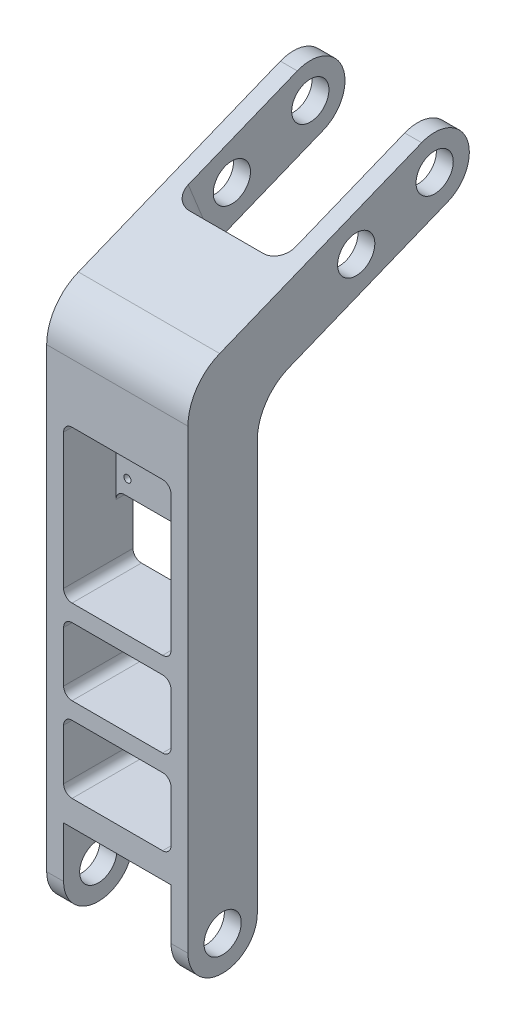
SolidWorks part; units mm, degrees
ref_plane "前视基准面" through (0, 0, 0) normal (0, 0, 1) x (1, 0, 0)
ref_plane "上视基准面" through (0, 0, 0) normal (0, 1, 0) x (1, 0, 0)
ref_plane "右视基准面" through (0, 0, 0) normal (1, 0, 0) x (0, 0, -1)
sketch "草图1" plane through (0, 0, 0) normal (0, 0, 1) x (1, 0, 0)
  line L0 (0, 0) -> (0, 40)
  line L1 (0, 40) -> (83.5, 40)
  line L2 (83.5, 40) -> (83.5, 0)
  line L3 (83.5, 0) -> (73.5, 0)
  line L4 (73.5, 0) -> (73.5, 30)
  line L5 (73.5, 30) -> (10, 30)
  line L6 (10, 30) -> (10, 0)
  line L7 (10, 0) -> (0, 0)
  dimension "D1" = 63.5
  dimension "D2" = 10
  dimension "D3" = 30
  dimension "D4" = 10
extrude "凸台-拉伸1" add sketch "草图1" along normal blind 41
sketch "草图2" plane through (83.5, 0, 0) normal (1, 0, 0) x (0, 0, -1)
  line L0 (-41, 0) -> (0, 0)
  arc A0 (-41, 0) -> (0, 0) centre (-20.5, 0) ccw
extrude "凸台-拉伸2" add sketch "草图2" against normal blind 10
sketch "草图3" plane through (83.5, 0, 0) normal (1, 0, 0) x (0, 0, -1)
  circle A0 centre (-20.5, 0) radius 11
  dimension "D1" = 22
extrude "切除-拉伸1" cut sketch "草图3" against normal blind 10
ref_plane "基准面4" through (41.75, 0, 0) normal (1, 0, 0) x (0, 0, -1)
mirror "镜向1" about plane through (41.75, 0, 0) normal (1, 0, 0) of "凸台-拉伸2", "切除-拉伸1"
sketch "草图4" plane through (0, 40, 0) normal (0, 1, 0) x (1, 0, 0)
  line L0 (83.5, 0) -> (0, 0) construction
  line L1 (0, 0) -> (83.5, 0)
  line L2 (0, 0) -> (0, -41)
  line L3 (0, -41) -> (83.5, -41)
  line L4 (83.5, 0) -> (83.5, -41)
  line L5 (83.5, -41) -> (0, -41) construction
  line L6 (41.75, -41) -> (41.75, 5.4834) construction
extrude "凸台-拉伸3" add sketch "草图4" along normal blind 250
sketch "草图5" plane through (0, 0, 41) normal (0, 0, 1) x (1, 0, 0)
  line L0 (83.5, 0) -> (83.5, 290) construction
  line L1 (15, 45) -> (68.5, 45)
  line L2 (10, 50) -> (10, 80)
  line L3 (15, 85) -> (68.5, 85)
  line L4 (73.5, 50) -> (73.5, 80)
  line L5 (0, 290) -> (0, 0) construction
  line L6 (10, 30) -> (73.5, 30) construction
  line L23 (10, 100) -> (10, 130)
  line L24 (15, 95) -> (68.5, 95)
  line L25 (73.5, 100) -> (73.5, 130)
  line L26 (15, 135) -> (68.5, 135)
  line L27 (10, 150) -> (10, 180)
  line L28 (15, 145) -> (68.5, 145)
  line L29 (73.5, 150) -> (73.5, 180)
  line L30 (15, 185) -> (68.5, 185)
  arc A0 (68.5, 45) -> (73.5, 50) centre (68.5, 50) ccw
  arc A1 (68.5, 85) -> (73.5, 80) centre (68.5, 80) cw
  arc A2 (15, 45) -> (10, 50) centre (15, 50) cw
  arc A3 (10, 80) -> (15, 85) centre (15, 80) cw
  arc A20 (10, 130) -> (15, 135) centre (15, 130) cw
  arc A21 (15, 95) -> (10, 100) centre (15, 100) cw
  arc A22 (68.5, 95) -> (73.5, 100) centre (68.5, 100) ccw
  arc A23 (68.5, 135) -> (73.5, 130) centre (68.5, 130) cw
  arc A24 (10, 180) -> (15, 185) centre (15, 180) cw
  arc A25 (15, 145) -> (10, 150) centre (15, 150) cw
  arc A26 (68.5, 145) -> (73.5, 150) centre (68.5, 150) ccw
  arc A27 (68.5, 185) -> (73.5, 180) centre (68.5, 180) cw
  point P10 (73.5, 45)
  point P13 (73.5, 85)
  dimension "D4" = 5
  dimension "D1" = 10
  dimension "D2" = 10
  dimension "D3" = 40
  dimension "D5" = 15
  dimension "D6" = 3
extrude "切除-拉伸2" cut sketch "草图5" against normal blind 309
sketch "草图7" plane through (83.5, 0, 0) normal (1, 0, 0) x (0, 0, -1)
  line L0 (0, 262.3452) -> (112.4864, 307.7926)
  line L1 (112.4864, 307.7926) -> (97.1275, 345.8071)
  line L2 (97.1275, 345.8071) -> (-41, 290)
  line L3 (-41, 290) -> (0, 262.3452)
  line L4 (0, 0) -> (0, 290) construction
  circle A1 centre (-20.5, 0) radius 11 construction
  point P3 (104.807, 326.7999)
  dimension "D1" = 350
  dimension "D2" = 112
  dimension "D3" = 41
extrude "凸台-拉伸5" add sketch "草图7" against normal up to surface (83.5 mm away) up to face at (0, 11, 20.5)
sketch "草图8" plane through (41.75, 0, 0) normal (1, 0, 0) x (0, 0, -1)
  line L0 (0, 232.3452) -> (0, 192.3452)
  line L1 (55, 192.3452) -> (55, 210.3452)
  line L2 (0, 192.3452) -> (55, 192.3452)
  line L5 (55, 210.3452) -> (0, 232.3452)
  line L7 (0, 0) -> (0, 262.3452) construction
  dimension "D1" = 70
  dimension "D2" = 55
  dimension "D3" = 40
  dimension "D4" = 18
extrude "凸台-拉伸6" add sketch "草图8" along normal mid plane 83.5
fillet "圆角1" radius 8 1 edges at (41.75, 192.3452, -55)
sketch "草图10" plane through (83.5, 0, 0) normal (1, 0, 0) x (0, 0, -1)
  circle A0 centre (47, 200.3452) radius 5.5
  dimension "D1" = 11
extrude "切除-拉伸3" cut sketch "草图10" against normal blind 92
sketch "草图11" [suppressed] plane through (52.25, 0, 0) normal (1, 0, 0) x (0, 0, -1)
  line L0 (55, 283.0172) -> (15, 241.915)
  line L1 (55, 242.0172) -> (55, 298.0172) construction
  line L2 (15, 241.915) -> (15, 227.0172)
  line L3 (0, 227.0172) -> (40, 227.0172) construction
  line L4 (15, 227.0172) -> (64.4389, 227.0172)
  line L5 (64.4389, 227.0172) -> (55, 283.0172)
  line L6 (0, 0) -> (0, 243.0172) construction
  dimension "D1" = 15
  dimension "D2" = 15
fillet "圆角2" [suppressed] radius 5
sketch "草图13" plane through (41.75, 0, 0) normal (1, 0, 0) x (0, 0, -1)
  circle A0 centre (47, 200.3452) radius 6
  circle A1 centre (47, 200.3452) radius 5
  dimension "D1" = 10
extrude "凸台-拉伸8" [suppressed] add sketch "草图13" along normal mid plane 1
sketch "草图14" plane through (41.75, 0, 0) normal (1, 0, 0) x (0, 0, -1)
  line L0 (97.1275, 345.8071) -> (112.4864, 307.7926)
  arc A0 (97.1275, 345.8071) -> (112.4864, 307.7926) centre (104.807, 326.7999) cw
extrude "凸台-拉伸9" add sketch "草图14" against normal mid plane 83.5
sketch "草图15" plane through (83.5, 0, 0) normal (1, 0, 0) x (0, 0, -1)
  line L0 (0, 262.3452) -> (112.4864, 307.7926) construction
  circle A0 centre (104.807, 326.7999) radius 11
  circle A1 centre (58.4478, 308.0696) radius 11
  dimension "D1" = 22
  dimension "D2" = 22
  dimension "D3" = 50
  dimension "D4" = 20.5
extrude "切除-拉伸5" cut sketch "草图15" against normal mid plane 185
sketch "草图16" plane through (0, 263.5448, 106.479) normal (0, 0.9272, 0.3746) x (1, 0, 0)
  line L0 (83.5, 240.0967) -> (0, 240.0967) construction
  line L1 (10, 240.0967) -> (73.5, 240.0967)
  line L2 (10, 240.0967) -> (10, 140.0967)
  line L3 (10, 140.0967) -> (73.5, 140.0967)
  line L4 (73.5, 240.0967) -> (73.5, 140.0967)
  line L5 (83.5, 219.5967) -> (83.5, 70.6214) construction
  line L6 (0, 70.6214) -> (0, 219.5967) construction
  dimension "D1" = 10
  dimension "D2" = 10
  dimension "D3" = 100
extrude "切除-拉伸6" cut sketch "草图16" against normal blind 65
sketch "草图17" plane through (10, 0, 0) normal (1, 0, 0) x (0, 0, -1)
  circle A0 centre (58.4478, 308.0696) radius 9.5
  circle A1 centre (58.4478, 308.0696) radius 7.5
  dimension "D1" = 15
extrude "凸台-拉伸10" [suppressed] add sketch "草图17" against normal blind 4
sketch "草图18" [suppressed] plane through (73.5, 0, 0) normal (-1, 0, 0) x (0, 0, 1)
  circle A0 centre (-35.6394, 310.5764) radius 7.5
  circle A1 centre (-35.6394, 310.5764) radius 9.5
extrude "凸台-拉伸11" [suppressed] add sketch "草图18" against normal blind 4
fillet "圆角3" radius 30 2 edges at (41.75, 290, 41) (41.75, 262.3452, 0)
extrude "切除-拉伸7" cut sketch "草图8<2>" against normal mid plane 75.5
sketch "草图8<2>" plane through (41.75, 0, 0) normal (1, 0, 0) x (0, 0, -1) same geometry as "草图8"
fillet "圆角4" [suppressed] radius 8
sketch "草图19" plane through (83.5, 0, 0) normal (1, 0, 0) x (0, 0, -1)
  line L1 (0, 232.3452) -> (70.1752, 232.3452)
  line L2 (0, 232.3452) -> (0, 190.676)
  line L3 (0, 190.676) -> (70.1752, 190.676)
  line L4 (70.1752, 232.3452) -> (70.1752, 190.676)
extrude "切除-拉伸8" cut sketch "草图19" against normal blind 90.5
sketch "草图20" plane through (0, 0, 0) normal (0, 0, -1) x (-1, 0, 0)
  line L1 (-66.75, 214) -> (-16.75, 214) construction
  line L2 (-66.75, 214) -> (-66.75, 194) construction
  line L3 (-66.75, 194) -> (-16.75, 194) construction
  line L4 (-16.75, 214) -> (-16.75, 194) construction
  line L5 (-66.75, 214) -> (-16.75, 194) construction
  line L6 (-66.75, 194) -> (-16.75, 214) construction
  point P0 (-41.75, 204)
  dimension "D1" = 41.75
  dimension "D2" = 204
  dimension "D3" = 20
  dimension "D4" = 50
hole_wizard "M5 螺纹孔的螺纹孔钻头1" positions "3D草图1" profile "草图21" hole size "M5" standard "GB"
sketch3d "3D草图1"
  point P0 (66.75, 214, 0)
  point P3 (16.75, 214, 0)
  point P6 (16.75, 194, 0)
  point P9 (66.75, 194, 0)
sketch "草图21" plane through (66.75, 214, 0) normal (1, 0, 0) x (0, 1, 0)
  line L0 (0, 0) -> (0, 11.2618)
  line L1 (0, 11.2618) -> (2.1, 10)
  line L2 (2.1, 10) -> (2.1, 0)
  line L5 (2.1, 0) -> (0, 0)
  line L10 (0, 11.2618) -> (-2.1, 10) construction
  line L11 (0, -6.35) -> (0, 107.95) construction
  dimension "孔直径" = 4.2
  dimension "孔深度" = 10
  dimension "导头角度" = 118
fillet "圆角5" radius 10 2 edges at (10, 297.0187, -31.0959) (73.5, 297.0187, -31.0959)
sketch "草图22" plane through (0, 0, 41) normal (0, 0, 1) x (1, 0, 0)
  line L2 (10, 190) -> (10, 230)
  line L3 (15, 235) -> (68.5, 235)
  line L4 (73.5, 190) -> (73.5, 230)
  line L5 (10, 190) -> (10, 177.9025)
  line L6 (10, 180) -> (10, 150) construction
  line L7 (73.5, 150) -> (73.5, 180) construction
  line L8 (10, 177.9025) -> (73.5, 177.9025)
  line L9 (73.5, 177.9025) -> (73.5, 190)
  arc A0 (10, 230) -> (15, 235) centre (15, 230) cw
  arc A1 (68.5, 235) -> (73.5, 230) centre (68.5, 230) cw
  point P10 (73.5, 235)
  point P13 (73.5, 185)
  dimension "D3" = 5
  dimension "D2" = 50
extrude "切除-拉伸9" cut sketch "草图22" against normal blind 31
sketch "草图23" plane through (83.5, 0, 0) normal (1, 0, 0) x (0, 0, -1)
  line L0 (-20.5, 0) -> (104.807, 326.7999) construction
  line L1 (104.807, 326.7999) -> (-20.5, 276.1726) construction
  line L2 (-20.5, 276.1726) -> (-20.5, 0) construction
  line L3 (97.1275, 345.8071) -> (-22.2382, 297.5803) construction
  dimension "D1" = 112
  dimension "D2" = 20.979
